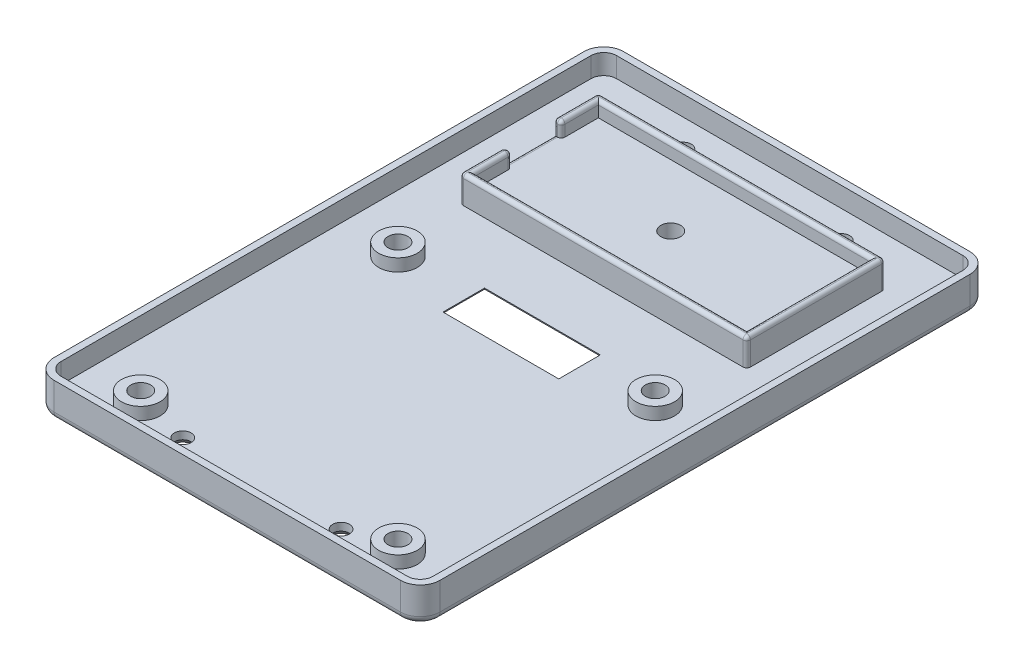
SolidWorks part; units mm, degrees
ref_plane "Plan de face" through (0, 0, 0) normal (0, 0, 1) x (1, 0, 0)
ref_plane "Plan de dessus" through (0, 0, 0) normal (0, 1, 0) x (1, 0, 0)
ref_plane "Plan de droite" through (0, 0, 0) normal (1, 0, 0) x (0, 0, -1)
sketch "Esquisse1" plane through (0, 0, 0) normal (0, 1, 0) x (1, 0, 0)
  line L1 (-39, 0) -> (39, 0)
  line L2 (-39, 0) -> (-39, 115.1)
  line L3 (-39, 115.1) -> (39, 115.1)
  line L4 (39, 0) -> (39, 115.1)
  point P4 (0, 0)
  dimension "D1" = 78
  dimension "D2" = 115.1
extrude "Bottom_WithPCB" add sketch "Esquisse1" along normal blind 7.05
fillet "Box_Corners" radius 4 4 edges at (39, 3.525, -115.1) (-39, 3.525, -115.1) (-39, 3.525, 0) (39, 3.525, 0)
fillet "Congé2" radius 1.5 8 edges at (-37.8284, 0, -113.9284) (-39, 0, -57.55) (-37.8284, 0, -1.1716) (0, 0, 0) (37.8284, 0, -1.1716) (39, 0, -57.55) (37.8284, 0, -113.9284) (0, 0, -115.1)
shell "Inside_Hole" thickness 3 removed face at (0, 7.05, -57.55)
sketch "Esquisse5" plane through (0, 7.05, 0) normal (0, 1, 0) x (1, 0, 0)
  line L8 (37.6, 4) -> (37.6, 111.1)
  line L9 (35, 113.7) -> (-35, 113.7)
  line L10 (-37.6, 111.1) -> (-37.6, 4)
  line L11 (-35, 1.4) -> (35, 1.4)
  line L12 (37.6, 4) -> (37.6, 111.1)
  line L13 (35, 113.7) -> (-35, 113.7)
  line L14 (-37.6, 111.1) -> (-37.6, 4)
  line L15 (-35, 1.4) -> (35, 1.4)
  arc A8 (37.6, 111.1) -> (35, 113.7) centre (35, 111.1) ccw
  arc A9 (37.6, 111.1) -> (35, 113.7) centre (35, 111.1) ccw
  arc A10 (-35, 113.7) -> (-37.6, 111.1) centre (-35, 111.1) ccw
  arc A11 (-35, 113.7) -> (-37.6, 111.1) centre (-35, 111.1) ccw
  arc A12 (-37.6, 4) -> (-35, 1.4) centre (-35, 4) ccw
  arc A13 (-37.6, 4) -> (-35, 1.4) centre (-35, 4) ccw
  arc A14 (35, 1.4) -> (37.6, 4) centre (35, 4) ccw
  arc A15 (35, 1.4) -> (37.6, 4) centre (35, 4) ccw
  dimension "D1" = 1.4
extrude "Border_Notch" cut sketch "Esquisse5" against normal blind 4.05
sketch "Col_Position" plane through (0, 3, 0) normal (0, 1, 0) x (1, 0, 0)
  circle A0 centre (-26, 8.5) radius 3.9
  dimension "D1" = 7.8
  dimension "D2" = 26
  dimension "D3" = 8.5
extrude "Col_PCB" add sketch "Col_Position" along normal blind 2.5
sketch "Esquisse4" plane through (0, 5.5, 0) normal (0, 1, 0) x (1, 0, 0)
  circle A0 centre (-26, 8.5) radius 2
  dimension "D1" = 4
extrude "Insert_Hole_In_Col" cut sketch "Esquisse4" against normal blind 4
mirror "Symétrie1" about plane through (0, 0, 0) normal (1, 0, 0) of "Col_PCB", "Insert_Hole_In_Col"
pattern_linear "Répétition linéaire1" count 2 spacing 52 along (0, 0, -1) of "Symétrie1"
hole_wizard "Fraisage pour vis à tête fraisée M31" positions "Esquisse6" profile "Esquisse7" countersink size "M3" standard "Ansi Metric" end condition through all
sketch "Esquisse6" plane through (0, 0, 0) normal (0, -1, 0) x (-1, 0, 0)
  line L1 (-16, 7) -> (16, 7) construction
  line L2 (16, 7) -> (16, 108.1) construction
  line L3 (16, 108.1) -> (-16, 108.1) construction
  line L4 (-16, 108.1) -> (-16, 7) construction
  line L6 (0, 0) -> (0, 7) construction
  point P0 (-16, 7)
  point P2 (16, 7)
  point P4 (16, 108.1)
  point P6 (-16, 108.1)
  dimension "D2" = 32
  dimension "D3" = 108.1
sketch "Esquisse7" plane through (16, 0, -7) normal (1, 0, 0) x (0, 0, -1)
  line L0 (0, 0) -> (0, 7.05)
  line L1 (0, 7.05) -> (1.7, 7.05)
  line L2 (1.7, 7.05) -> (1.7, 1.45)
  line L3 (1.7, 1.45) -> (3.15, 0)
  line L5 (3.15, 0) -> (0, 0)
  line L6 (-1.7, 1.45) -> (-3.15, 0) construction
  line L11 (0, -6.35) -> (0, 107.95) construction
  dimension "Diamètre du perçage jusqu'au prochain" = 3.4
  dimension "Profondeur du perçage jusqu'au prochain" = 7.05
  dimension "Diamètre du fraisage entrant" = 6.3
  dimension "Angle du fraisage entrant" = 90
sketch "Esquisse8" plane through (0, 3, 0) normal (0, 1, 0) x (1, 0, 0)
  line L0 (-22.1, 60.5) -> (22.1, 60.5) construction
  line L1 (-11.7, 59.5) -> (11.7, 59.5) construction
  line L2 (-11.7, 55.3) -> (11.7, 55.3)
  line L3 (-11.7, 55.3) -> (-11.7, 63.7)
  line L4 (-11.7, 63.7) -> (11.7, 63.7)
  line L5 (11.7, 55.3) -> (11.7, 63.7)
  line L6 (0, 60.5) -> (0, 59.5) construction
  circle A0 centre (-26, 60.5) radius 3.9 construction
  circle A1 centre (-26, 60.5) radius 3.9 construction
  circle A2 centre (26, 60.5) radius 3.9 construction
  dimension "D1" = 23.4
  dimension "D2" = 8.4
extrude "Solar_Opening" cut sketch "Esquisse8" against normal through all
chamfer "Chanfrein1" distance 2.8 angle 45 4 edges at (-11.7, 0, -59.5) (0, 0, -55.3) (0, 0, -63.7) (11.7, 0, -59.5)
sketch "Esquisse9" plane through (0, 3, 0) normal (0, 1, 0) x (1, 0, 0)
  line L0 (-29, 76) -> (29, 76) construction
  line L1 (29, 76) -> (29, 104) construction
  line L2 (29, 104) -> (-29, 104) construction
  line L3 (-29, 104) -> (-29, 76) construction
  line L4 (-29, 90) -> (29, 90) construction
  line L5 (0, 76) -> (0, 0) construction
  line L6 (-29, 104) -> (-29, 90)
  line L14 (-29, 90) -> (-29, 76)
  line L15 (-29, 76) -> (29, 76)
  line L16 (29, 76) -> (29, 104)
  line L17 (29, 104) -> (-29, 104)
  dimension "D1" = 58
  dimension "D2" = 28
  dimension "D3" = 76
extrude "Boss.-Extru.1" add sketch "Esquisse9" along normal blind 2.5
sketch "Esquisse10" plane through (0, 5.5, 8) normal (0, 1, 0) x (1, 0, 0)
  line L0 (-29, 84) -> (29, 84) construction
  line L1 (29, 84) -> (29, 112) construction
  line L2 (29, 112) -> (-29, 112) construction
  line L3 (-29, 112) -> (-29, 84) construction
  line L4 (-29, 98) -> (29, 98) construction
  line L5 (0, 84) -> (0, 8) construction
  line L6 (-29, 112) -> (-29, 103)
  line L7 (-29, 103) -> (-27.5, 103)
  line L8 (-27.5, 103) -> (-27.5, 110.5)
  line L9 (-27.5, 110.5) -> (27.5, 110.5)
  line L10 (27.5, 110.5) -> (27.5, 85.5)
  line L11 (27.5, 85.5) -> (-27.5, 85.5)
  line L12 (-27.5, 85.5) -> (-27.5, 93)
  line L13 (-27.5, 93) -> (-29, 93)
  line L14 (-29, 93) -> (-29, 84)
  line L15 (-29, 84) -> (29, 84)
  line L16 (29, 84) -> (29, 112)
  line L17 (29, 112) -> (-29, 112)
  line L18 (-27.5, 103) -> (-27.5, 93) construction
  line L19 (27.5, 85.5) -> (27.5, 84) construction
  line L20 (27.5, 110.5) -> (27.5, 112) construction
  line L21 (-27.5, 110.5) -> (-29, 110.5) construction
  line L22 (-27.5, 85.5) -> (-29, 85.5) construction
  line L23 (27.5, 85.5) -> (29, 85.5) construction
  point P18 (-27.5, 98)
  dimension "D1" = 58
  dimension "D2" = 28
  dimension "D3" = 76
  dimension "D4" = 1.5
  dimension "D5" = 10
extrude "Boss.-Extru.2" add sketch "Esquisse10" along normal blind 3
fillet "Congé3" radius 0.75 21 edges at (-29, 5.75, -104) (29, 5.75, -104) (29, 5.75, -76) (-29, 5.75, -76) (-29, 7, -85) (-27.5, 7, -85) (-27.5, 7, -95) (-29, 7, -95) (-29, 8.5, -80.5) (-27.5, 8.5, -81.25) (0, 8.5, -77.5) (27.5, 8.5, -90) (0, 8.5, -102.5) (-27.5, 8.5, -98.75) (-29, 8.5, -99.5) (0, 8.5, -104) (29, 8.5, -90) (0, 8.5, -76) (-29, 5.5, -90) (-28.25, 8.5, -85) (-28.25, 8.5, -95)
sketch "Esquisse11" plane through (0, 5.5, 0) normal (0, 1, 0) x (1, 0, 0)
  line L0 (-28.25, 90) -> (27.5, 90) construction
  line L1 (-28.25, 95) -> (-28.25, 85) construction
  line L2 (27.5, 102.5) -> (27.5, 77.5) construction
  circle A0 centre (-0.375, 90) radius 2
  dimension "D1" = 4
extrude "Enlèv. mat.-Extru.1" cut sketch "Esquisse11" against normal blind 4
sketch "Esquisse12" plane through (0, 0, 0) normal (0, -1, 0) x (1, 0, 0)
  line L1 (37.5, -111.1) -> (37.5, -4) construction
  line L4 (37.5, -37.2) -> (37.5, -91.75) construction
  line L6 (-37.5, -37.2) -> (37.5, -37.2) construction
  line L7 (-37.5, -4) -> (-37.5, -111.1) construction
  line L10 (-37.5, -91.75) -> (37.5, -91.75) construction
  text T0 "ETML-ES\r\nSLO2-23" font "Consolas" height 8
  text T1 "\r\nMiguel Santos" font "Century Gothic" height 6
  text T2 "2228 Alarme fenêtre V1" font "Century Gothic" height 4
  dimension "D1" = 37.2
  dimension "D2" = 54.55
extrude "Enlèv. mat.-Extru.2" cut sketch "Esquisse12" against normal blind 0.4
equation "\"PCB_Length_Y\"= 60mm"
equation "\"PCB_Width_X\"= 60mm"
equation "\"PCB_Thickness_Z\"= 1.55mm"
equation "\"PCB_Pos_Y\"= 5mm"
equation "\"PCB_Zone_Y\"= \"PCB_Length_Y\" + \"Box_Wall_Thickness\" 'Zone occupée par le PCB centrée au milieu de la zone"
equation "\"PCB_Zone_X\"= \"PCB_Width_X\" + 12mm"
equation "\"Battery_Zone_Y\"= \"Battery_Length_Y\" + \"Box_Wall_Thickness\" + \"Fixation_holes_offset\" + \"Col_Diameter\"/2 + \"Battery_Offset\" + \"Global_Gap\"*2"
equation "\"Battery_Length_Y\"= 25mm"
equation "\"Battery_Width_X\"= 55mm"
equation "\"Box_Wall_Thickness\"= 3mm"
equation "\"Box_Border_Height\"= \"Col_Height\" + \"PCB_Thickness_Z\""
equation "\"Box_Corner_Radius\"= 4mm"
equation "\"PCB_Holes_X\"= 52mm"
equation "\"PCB_Holes_Y\"= 52mm"
equation "\"Col_Height\"= 2.5mm"
equation "\"Box_Bottom_Thick\"= 3mm"
equation "\"Box_Top_Thick\"= 3mm"
equation "\"PCB_Components_Height\"= 25mm"
equation "\"Global_Gap\"= 0.1mm"
equation "\"Col_Diameter\"= 7.8mm"
equation "\"D1@Esquisse1\"=\"PCB_Zone_X\"+2 * \"Box_Wall_Thickness\""
equation "\"D2@Esquisse1\"=2 * \"Box_Wall_Thickness\" + \"PCB_Zone_Y\" + \"Battery_Zone_Y\""
equation "\"D1@Bottom_WithPCB\" = \"Box_Bottom_Thick\" + \"Box_Border_Height\""
equation "\"D1@Box_Corners\"=\"Box_Corner_Radius\""
equation "\"D1@Inside_Hole\"=\"Box_Wall_Thickness\""
equation "\"D2@Inside_Hole\"= \"Box_Bottom_Thick\""
equation "\"D1@Col_Position\" = \"Col_Diameter\""
equation "\"D2@Col_Position\"= \"PCB_Holes_X\" / 2"
equation "\"D3@Col_Position\" =  ( \"PCB_Zone_Y\" - \"PCB_Holes_Y\" )  / 2 + \"Box_Wall_Thickness\""
equation "\"D1@Col_PCB\" = \"Col_Height\""
equation "\"D3@Répétition linéaire1\"=\"PCB_Holes_Y\""
equation "\"Inserts_Diameter\"= 4mm"
equation "\"Inserts_Height\"= 4mm"
equation "\"D1@Esquisse4\"=\"Inserts_Diameter\""
equation "\"D1@Insert_Hole_In_Col\" = \"Inserts_Height\""
equation "\"D1@Esquisse5\"=\"Box_Wall_Thickness\"/2 - \"Global_Gap\""
equation "\"D1@Border_Notch\" = \"Box_Border_Height\""
equation "\"Fixation_holes_X\"= 32mm"
equation "\"Fixation_holes_offset\"= 4mm'Distance from inside border of hole center"
equation "\"D2@Esquisse6\"=\"Fixation_holes_X\""
equation "\"Solar_Width_X\"= 23.4mm"
equation "\"Solar_Length_Y\"= 8.4mm"
equation "\"D1@Esquisse8\"=\"Solar_Width_X\""
equation "\"D2@Esquisse8\"=\"Solar_Length_Y\""
equation "\"D1@Chanfrein1\"=\"Box_Bottom_Thick\" - \"Global_Gap\"*2"
equation "\"D1@Congé2\"=\"Box_Bottom_Thick\"/2"
equation "\"D1@Esquisse6\"=\"Box_Wall_Thickness\"+\"Fixation_holes_offset\""
equation "\"D1@Esquisse9\"=\"Battery_Width_X\" + \"Box_Wall_Thickness\""
equation "\"D2@Esquisse9\"=\"Battery_Length_Y\" + \"Box_Wall_Thickness\""
equation "\"D1@Boss.-Extru.1\"=\"Col_Height\""
equation "\"D1@Congé3\"=\"Box_Wall_Thickness\"/4"
equation "\"D3@Esquisse6\"=\"Box_Wall_Thickness\" + \"PCB_Zone_Y\" + \"Battery_Zone_Y\" - \"Fixation_holes_offset\""
equation "\"D3@Esquisse9\"=\"Box_Wall_Thickness\"+\"PCB_Zone_Y\" + \"Battery_Offset\""
equation "\"Battery_Offset\"= 10mm"
equation "\"D1@Boss.-Extru.2\"=\"Box_Wall_Thickness\""
equation "\"D1@Esquisse11\"=\"Inserts_Diameter\""
equation "\"D1@Enlèv. mat.-Extru.1\"=\"Inserts_Height\""
equation "\"D1@Esquisse12\"=\"Box_Wall_Thickness\"+\"PCB_Zone_Y\"/1.5 - \"Col_Diameter\""
equation "\"D2@Esquisse12\"=(\"PCB_Zone_Y\"+\"Battery_Zone_Y\")/2"
equation "\"D3@Esquisse10\"=\"Box_Wall_Thickness\"+\"PCB_Zone_Y\" + \"Battery_Offset\""
equation "\"D1@Esquisse10\"=\"Battery_Width_X\" + \"Box_Wall_Thickness\""
equation "\"D2@Esquisse10\"=\"Battery_Length_Y\" + \"Box_Wall_Thickness\""
equation "\"D4@Esquisse10\"=\"Box_Wall_Thickness\"/2"
